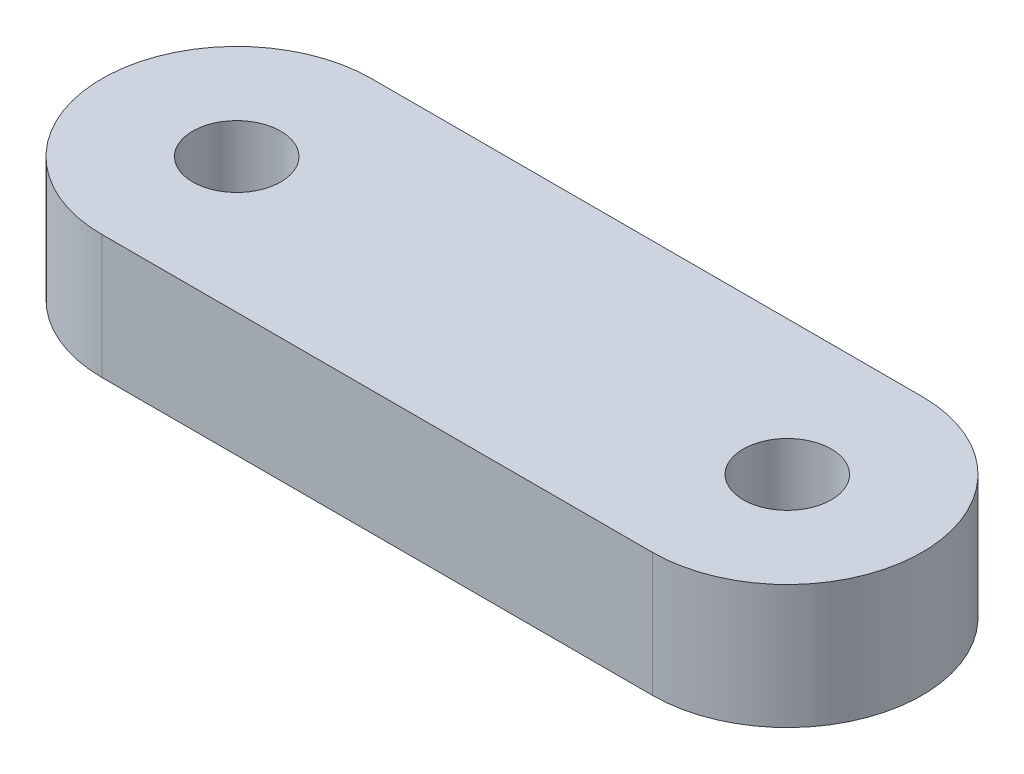
SolidWorks part; units mm, degrees
ref_plane "Front Plane" through (0, 0, 0) normal (0, 0, 1) x (1, 0, 0)
ref_plane "Top Plane" through (0, 0, 0) normal (0, 1, 0) x (1, 0, 0)
ref_plane "Right Plane" through (0, 0, 0) normal (1, 0, 0) x (0, 0, -1)
sketch "Sketch1" plane through (0, 0, 0) normal (0, 1, 0) x (1, 0, 0)
  line L0 (14.9, 0) -> (14.9, 15.5804) construction
  line L1 (-10, 4.9) -> (10, 4.9)
  line L2 (-14.9, 0) -> (-14.9, 15.5804) construction
  line L3 (-10, -4.9) -> (10, -4.9)
  line L4 (-10, 4.9) -> (-10, -4.9) construction
  line L5 (-10, 4.9) -> (10, -4.9) construction
  line L6 (-10, -4.9) -> (10, 4.9) construction
  line L7 (10, 4.9) -> (10, -4.9) construction
  line L8 (0, 4.9) -> (0, -4.9) construction
  arc A0 (-10, 4.9) -> (-10, -4.9) centre (-10, 0) ccw
  arc A1 (10, -4.9) -> (10, 4.9) centre (10, 0) ccw
  circle A2 centre (-10, 0) radius 1.6
  circle A3 centre (10, 0) radius 1.6
  point P0 (0, 0)
  dimension "D4" = 4.9
  dimension "D5" = 3.2
  dimension "D1" = 9.8
  dimension "D2" = 20
extrude "Boss-Extrude1" add sketch "Sketch1" along normal blind 4.5
equation "\"Y-ROD-SPACING\"=75"
equation "\"Y-BED-OFFSET\"=2"
equation "\"Y-BED-ROD-INSET\"=3.5"
equation "\"T-SLOT-NUT-FILLET-RADIUS\"=0.25"
equation "\"T-SLOT-SCREW-SHAFT-RADIUS\"=1.75"
equation "\"T-SLOT-SCREW-SHAFT-CUTOUT-LENGTH\"=10.5"
equation "\"T-SLOT-NUT-DEPTH\"=4.2"
equation "\"T-SLOT-NUT-WIDTH\"=3"
equation "\"T-SLOT-NUT-END-DISTANCE\"=8"
equation "\"ACRYLIC-TAB-CUTOUT-SIZE\"=\"ACRYLIC-THICKNESS\"+\"ACRYLIC-TAB-TOLERANCE\"*2"
equation "\"ACRYLIC-M3-HOLE\"=3.2"
equation "\"D5@Sketch1\"=\"ACRYLIC-M3-HOLE\""
equation "\"SMOOTHROD-CAP-SCREW-DISTANCE\"=20"
equation "\"D2@Sketch1\"=\"SMOOTHROD-CAP-SCREW-DISTANCE\""
equation "\"X-ROD-SPACING\"=45"
equation "\"Z-ROD-SPACING\"=17.5"
equation "\"ACRYLIC-THICKNESS\"=10"
equation "\"ACRYLIC-THICKNESS2\"=4.5"
equation "\"ACRYLIC-TAB-WIDTH\"=\"ACRYLIC-THICKNESS\""
equation "\"FRAME-WIDTH-INNER\"=370"
equation "\"NEMA17-HOLE-SPACING\"=31"
equation "\"NEMA17-CENTRAL-CUTOUT\"=22.5"
equation "\"Z-BRACKET-REACH\"=55"
equation "\"TOP-BRACKET-SPACING\"=40"
equation "\"SMOOTHROD-X-LENGTH\"=350"
equation "\"SMOOTHROD-Y-LENGTH\"=350"
equation "\"SMOOTHROD-Z-LENGTH\"=350"
equation "\"SMOOTHROD-TIGHTENING-HEADROOM\"=1"
equation "\"LEADSCREW-Z-LENGTH\"=300"
equation "\"SCREW-LENGTH-FRAME\"=\"ACRYLIC-THICKNESS\" + 10"
equation "\"SCREW-HEAD-RADIUS\"=6"
equation "\"PRINTED-X-SMOOTHROD-DIAMETER\"=8.2"
equation "\"PRINTED-X-SMOOTHROD-CUTOUT\"=10"
equation "\"PRINTED-X-BASE-HEIGHT\"=10"
equation "\"PRINTED-LM8UU-CUTOUT-SIZE\"=16"
equation "\"PRINTED-LM8UU-CUTOUT-LENGTH\"=24.5"
equation "\"PRINTED-X-IDLER-HEIGHT\"=16"
equation "\"PSU-MOUNTING-WIDTH\"=95"
equation "\"PSU-MOUNTING-HEIGHT\"=177"
equation "\"D1@Boss-Extrude1\"=\"ACRYLIC-THICKNESS2\""
